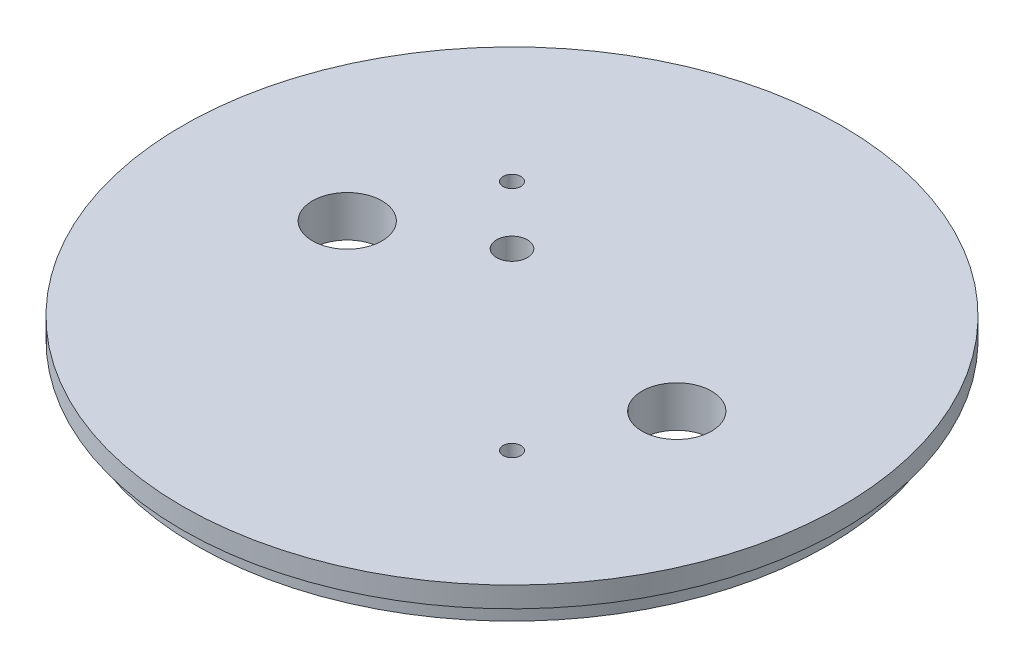
SolidWorks part; units mm, degrees
material "6061-T4 (SS)"
ref_plane "Front Plane" through (0, 0, 0) normal (0, 0, 1) x (1, 0, 0)
ref_plane "Top Plane" through (0, 0, 0) normal (0, 1, 0) x (1, 0, 0)
ref_plane "Right Plane" through (0, 0, 0) normal (1, 0, 0) x (0, 0, -1)
sketch "Sketch1" plane through (0, 0, 0) normal (0, 1, 0) x (1, 0, 0)
  line L0 (0, -50.8) -> (0, 50.8) construction
  line L1 (-50.8, 0) -> (50.8, 0) construction
  line L2 (-17.9605, 17.9605) -> (0, 0) construction
  line L3 (0, 56.7387) -> (0, 29.6936) construction
  line L4 (3.6407, 56.7387) -> (3.6407, 29.6936) construction
  line L5 (-3.6407, 56.7387) -> (-3.6407, 29.6936) construction
  line L6 (0, -56.7387) -> (0, -29.6936) construction
  line L7 (3.6407, -56.7387) -> (3.6407, -29.6936) construction
  line L8 (-3.6407, -56.7387) -> (-3.6407, -29.6936) construction
  line L9 (-35.921, -35.921) -> (54.3236, 54.3236) construction
  circle A0 centre (0, 0) radius 50.8
  circle A1 centre (0, 0) radius 3.175 construction
  circle A2 centre (25.4, 0) radius 5.3578
  circle A3 centre (-25.4, 0) radius 5.3578
  circle A4 centre (-17.9605, 17.9605) radius 1.3589
  arc A6 (3.6407, 56.7387) -> (-3.6407, 56.7387) centre (0, 56.7387) ccw construction
  arc A7 (-3.6407, 29.6936) -> (3.6407, 29.6936) centre (0, 29.6936) ccw construction
  arc A8 (3.6407, -56.7387) -> (-3.6407, -56.7387) centre (0, -56.7387) cw construction
  arc A9 (-3.6407, -29.6936) -> (3.6407, -29.6936) centre (0, -29.6936) cw construction
  circle A10 centre (17.9605, -17.9605) radius 1.3589
  circle A11 centre (-8.9803, 8.9803) radius 2.3813
  circle A12 centre (8.9803, -8.9803) radius 2.3813 construction
  point P16 (0, 43.2162)
  point P19 (0, 0)
  point P26 (0, -43.2162)
  dimension "D1" = 101.6
  dimension "D2" = 6.35
  dimension "D3" = 10.7156
  dimension "D5" = 2.7178
  dimension "D8" = 4.7625
  dimension "D6" = 25.4
  dimension "D7" = 45
  dimension "D4" = 45
  dimension "D9" = 25.4
extrude "Boss-Extrude1" add sketch "Sketch1" along normal blind 6.35
sketch "Sketch2" plane through (0, 0, 0) normal (0, -1, 0) x (1, 0, 0)
  circle A0 centre (0, 0) radius 50.8
  circle A1 centre (0, 0) radius 48.641
  dimension "D1" = 101.6
  dimension "D2" = 97.282
extrude "Cut-Extrude1" cut sketch "Sketch2" against normal blind 3.175
sketch "Sketch3" plane through (0, 6.35, 0) normal (0, 1, 0) x (1, 0, 0)
  line L0 (0, 50.8) -> (0, -50.8) construction
  line L1 (-50.8, 0) -> (50.8, 0) construction
  line L2 (0, 34.798) -> (0, 13.97) construction
  line L3 (3.2385, 34.798) -> (3.2385, 13.97)
  line L4 (-3.2385, 34.798) -> (-3.2385, 13.97)
  line L5 (0, -34.798) -> (0, -13.97) construction
  line L6 (3.2385, -34.798) -> (3.2385, -13.97)
  line L7 (-3.2385, -34.798) -> (-3.2385, -13.97)
  circle A0 centre (0, 0) radius 50.8 construction
  arc A1 (3.2385, 34.798) -> (-3.2385, 34.798) centre (0, 34.798) ccw
  arc A2 (-3.2385, 13.97) -> (3.2385, 13.97) centre (0, 13.97) ccw
  arc A3 (3.2385, -34.798) -> (-3.2385, -34.798) centre (0, -34.798) cw
  arc A4 (-3.2385, -13.97) -> (3.2385, -13.97) centre (0, -13.97) cw
  point P7 (0, 13.97)
  point P8 (0, 34.798)
  point P12 (0, 24.384)
  point P20 (0, -24.384)
  point P25 (0, -34.798)
  point P26 (0, -13.97)
  dimension "D1" = 13.97
  dimension "D2" = 20.828
  dimension "D3" = 6.477
extrude "Cut-Extrude2" cut sketch "Sketch3" against normal blind 3.556 from offset 2.794 offset against normal yes
equation "\"Lead_Screw_Dist\" = 2in"
equation "\"Coupler_OD\" = 3.899in"
equation "\"Coupler_ID\" = 3.755in"
equation "\"Lead_Screw_Hole_Diam\" = (27/64)*1in"
equation "\"D3@Sketch1\"=\"Lead_Screw_Hole_Diam\""
equation "\"D9@Sketch1\"=\"Lead_Screw_Dist\"/2"
